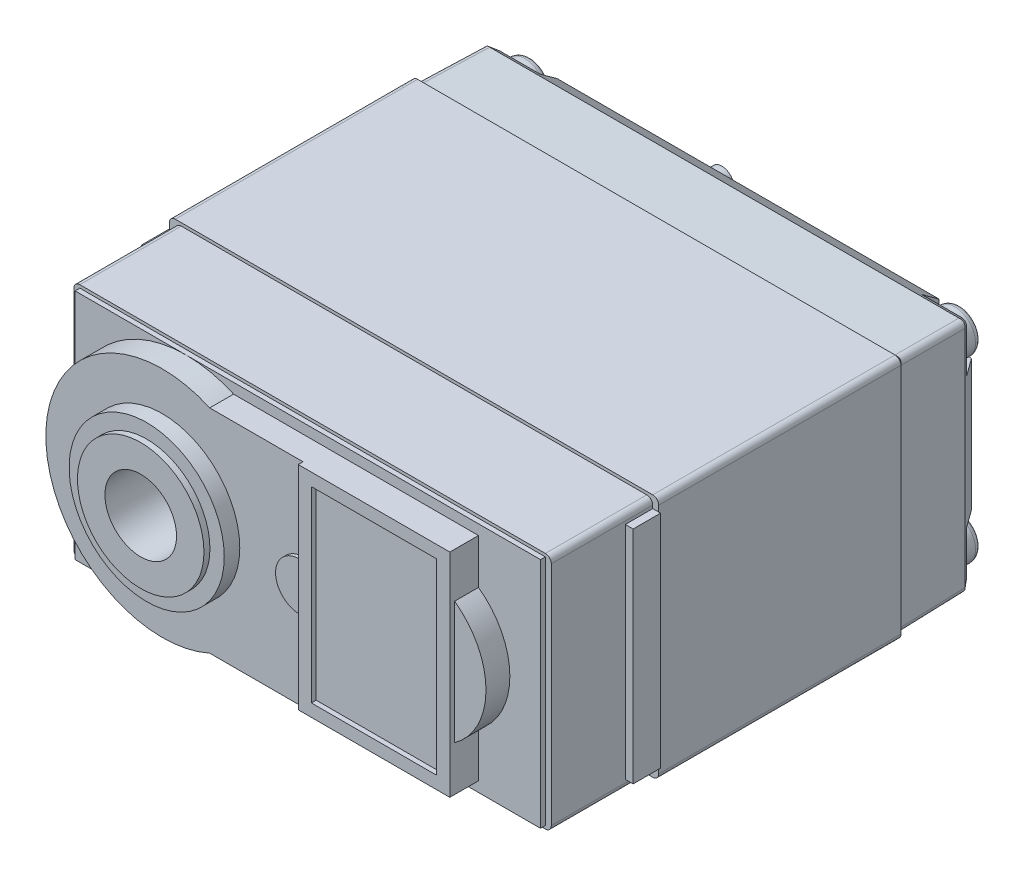
SolidWorks part; units mm, degrees
material "Du_servo"
ref_plane "Спереди" through (0, 0, 0) normal (0, 0, 1) x (1, 0, 0)
ref_plane "Сверху" through (0, 0, 0) normal (0, 1, 0) x (1, 0, 0)
ref_plane "Справа" through (0, 0, 0) normal (1, 0, 0) x (0, 0, -1)
sketch "Эскиз1" plane through (0, 0, 0) normal (0, 0, 1) x (1, 0, 0)
  line L1 (-20.5, 10.25) -> (20.5, 10.25)
  line L2 (-20.5, 10.25) -> (-20.5, -10.25)
  line L3 (-20.5, -10.25) -> (20.5, -10.25)
  line L4 (20.5, 10.25) -> (20.5, -10.25)
  line L5 (-20.5, 10.25) -> (20.5, -10.25) construction
  line L6 (-20.5, -10.25) -> (20.5, 10.25) construction
  point P0 (0, 0)
  dimension "D1" = 20.5
  dimension "D2" = 41
extrude "Бобышка-Вытянуть1" add sketch "Эскиз1" along normal blind 20.5
sketch "Эскиз2" plane through (0, 0, 20.5) normal (0, 0, 1) x (1, 0, 0)
  line L1 (-20, 10) -> (20, 10)
  line L2 (-20, 10) -> (-20, -10)
  line L3 (-20, -10) -> (20, -10)
  line L4 (20, 10) -> (20, -10)
  line L5 (-20, 10) -> (20, -10) construction
  line L6 (-20, -10) -> (20, 10) construction
  point P0 (0, 0)
  dimension "D1" = 20
  dimension "D2" = 40
extrude "Бобышка-Вытянуть2" add sketch "Эскиз2" along normal blind 8.5
sketch "Эскиз3" plane through (0, 0, 20.5) normal (0, 0, 1) x (1, 0, 0)
  line L0 (-20.5462, 9.25) -> (-20.5, -9.25)
  line L1 (-20.5462, 9.25) -> (20.6559, 9.25)
  line L3 (-20.5, -9.25) -> (20.6559, -9.25)
  line L5 (-20.5407, 7.0371) -> (20.6559, -7.0766) construction
  line L6 (-20.5056, -7.0251) -> (20.6559, 7.0766) construction
  line L7 (-20.5, 10.25) -> (-20.5, -10.25) construction
  line L8 (20.6559, 9.25) -> (20.6559, -9.25)
  point P0 (0, 0)
extrude "Бобышка-Вытянуть3" add sketch "Эскиз3" along normal blind 2.3
sketch "Эскиз4" plane through (0, 0, 0) normal (0, 0, -1) x (-1, 0, 0)
  line L1 (-20.25, 10) -> (20.25, 10)
  line L2 (-20.25, 10) -> (-20.25, -10)
  line L3 (-20.25, -10) -> (20.25, -10)
  line L4 (20.25, 10) -> (20.25, -10)
  line L5 (-20.25, 10) -> (20.25, -10) construction
  line L6 (-20.25, -10) -> (20.25, 10) construction
  point P0 (0, 0)
  dimension "D1" = 20
  dimension "D2" = 40.5
extrude "Бобышка-Вытянуть4" add sketch "Эскиз4" along normal blind 7.5 draft 1
sketch "Эскиз5" plane through (0, 0, 29) normal (0, 0, -1) x (-1, 0, 0)
  line L1 (-19.5, -9.75) -> (19.5, -9.75)
  line L2 (-19.5, -9.75) -> (-19.5, 9.75)
  line L3 (-19.5, 9.75) -> (19.5, 9.75)
  line L4 (19.5, -9.75) -> (19.5, 9.75)
  line L5 (-19.5, -9.75) -> (19.5, 9.75) construction
  line L6 (-19.5, 9.75) -> (19.5, -9.75) construction
  point P0 (0, 0)
  dimension "D1" = 19.5
  dimension "D2" = 39
extrude "Бобышка-Вытянуть5" add sketch "Эскиз5" against normal blind 0.4
sketch "Эскиз6" plane through (0, 0, 29.4) normal (0, 0, 1) x (1, 0, 0)
  line L1 (-28.6224, 0) -> (37.7217, 0) construction
  line L2 (-20.5462, 9.25) -> (-20.5, -9.25) construction
  line L3 (14.3, 8.9) -> (-6.2185, 8.9)
  line L4 (14.3, 8.9) -> (14.3, -8.9)
  line L5 (-19.5, -9.75) -> (-19.5, 9.75) construction
  line L6 (14.3, -8.9) -> (-6.2185, -8.9)
  circle A0 centre (-10.2, 0) radius 9.75 construction
  arc A1 (-6.2185, 8.9) -> (-6.2185, -8.9) centre (-10.2, 0) ccw
  point P13 (14.3, 0)
  dimension "D1" = 19.5
  dimension "D5" = 10.3231
  dimension "D3" = 8.9
  dimension "D4" = 33.8
extrude "Бобышка-Вытянуть6" add sketch "Эскиз6" along normal blind 2
sketch "Эскиз8" plane through (0, 0, 31.4) normal (0, 0, 1) x (1, 0, 0)
  line L1 (14.3, 8.9) -> (1.6, 8.9)
  line L2 (14.3, 8.9) -> (14.3, -8.9)
  line L3 (14.3, -8.9) -> (1.6, -8.9)
  line L4 (1.6, 8.9) -> (1.6, -8.9)
  line L5 (-6.2185, -8.9) -> (14.3, -8.9) construction
  line L6 (7.95, 8.9) -> (7.95, -8.9) construction
  line L8 (2.7, 7.85) -> (13.2, 7.85)
  line L9 (2.7, 7.85) -> (2.7, -7.85)
  line L10 (2.7, -7.85) -> (13.2, -7.85)
  line L11 (13.2, 7.85) -> (13.2, -7.85)
  line L12 (7.95, -7.85) -> (7.95, 7.85) construction
  line L13 (2.7, 0) -> (13.2, 0) construction
  point P10 (7.95, 0)
  dimension "D1" = 17.8
  dimension "D2" = 12.7
  dimension "D3" = 15.7
  dimension "D4" = 10.5
extrude "Бобышка-Вытянуть7" add sketch "Эскиз8" along normal blind 0.4
sketch "Эскиз9" plane through (0, 0, 31.4) normal (0, 0, 1) x (1, 0, 0)
  circle A0 centre (-10.2, 0) radius 6.5
  dimension "D1" = 13
extrude "Бобышка-Вытянуть8" add sketch "Эскиз9" along normal blind 1.3
sketch "Эскиз10" plane through (0, 0, 32.7) normal (0, 0, 1) x (1, 0, 0)
  circle A0 centre (-10.2, 0) radius 5.3
  dimension "D1" = 10.6
extrude "Бобышка-Вытянуть9" add sketch "Эскиз10" along normal blind 0.5
sketch "Эскиз11" plane through (0, 0, 33.2) normal (0, 0, 1) x (1, 0, 0)
  circle A0 centre (-10.2, 0) radius 3
  dimension "D1" = 6
extrude "Вырез-Вытянуть2" cut sketch "Эскиз11" against normal blind 5
sketch "Эскиз12" plane through (0, 0, 31.4) normal (0, 0, 1) x (1, 0, 0)
  line L0 (1.6, 8.9) -> (1.6, -8.9) construction
  line L1 (1.6, 2) -> (1.6, -2)
  circle A0 centre (1.6, 0) radius 2 construction
  arc A1 (1.6, 2) -> (1.6, -2) centre (1.6, 0) ccw
  dimension "D1" = 4
extrude "Бобышка-Вытянуть10" add sketch "Эскиз12" along normal blind 0.3
sketch "Эскиз13" plane through (0, 0, 29.4) normal (0, 0, 1) x (1, 0, 0)
  line L0 (14.3, -8.9) -> (14.3, 8.9) construction
  line L1 (14.3, -8.9) -> (14.3, 8.9) construction
  line L2 (14.3, 5.1324) -> (11.8319, 5.1324)
  line L3 (11.8319, 5.1324) -> (11.8319, -5.1324)
  line L4 (11.8319, -5.1324) -> (14.3, -5.1324)
  circle A0 centre (10.6069, 0) radius 6.323 construction
  arc A1 (14.3, 5.1324) -> (14.3, -5.1324) centre (10.6069, 0) cw
  dimension "D1" = 12.6459
extrude "Бобышка-Вытянуть11" add sketch "Эскиз13" along normal blind 2
fillet "Скругление3" radius 0.5 8 edges at (-20, -10, 24.75) (-20.5, -10.25, 10.25) (-20, 10, 24.75) (-20.5, 10.25, 10.25) (20.5, 10.25, 10.25) (20, 10, 24.75) (20.5, -10.25, 10.25) (20, -10, 24.75)
chamfer "Фаска3" distance 0.2 angle 45 8 edges at (0, 10.25, 0) (-20.3536, 10.1036, 0) (20.3536, 10.1036, 0) (-20.5, 0, 0) (20.5, 0, 0) (-20.3536, -10.1036, 0) (20.3536, -10.1036, 0) (0, -10.25, 0)
chamfer "Фаска4" distance 2 angle 35 4 edges at (0, -9.8691, -7.5) (20.1191, 0, -7.5) (0, 9.8691, -7.5) (-20.1191, 0, -7.5)
sketch "Эскиз15" plane through (0, 0, -7.5) normal (0, 0, -1) x (-1, 0, 0)
  line L0 (20, -7.5) -> (16, -7.5) construction
  line L1 (-18, 7.5) -> (18, 7.5) construction
  line L2 (-18, 7.5) -> (-18, -7.5) construction
  line L3 (-18, -7.5) -> (18, -7.5) construction
  line L4 (18, 7.5) -> (18, -7.5) construction
  line L5 (0, -7.5) -> (0, 7.5) construction
  line L6 (-18, 0) -> (18, 0) construction
  line L7 (-20, 9.5) -> (-16, 9.5)
  line L8 (-20, 9.5) -> (-20, 5.5)
  line L9 (-20, 5.5) -> (-16, 5.5)
  line L10 (-16, 9.5) -> (-16, 5.5)
  line L11 (-18, 5.5) -> (-18, 9.5) construction
  line L12 (-20, 7.5) -> (-16, 7.5) construction
  line L13 (20, 9.5) -> (16, 9.5)
  line L14 (20, 9.5) -> (20, 5.5)
  line L15 (20, 5.5) -> (16, 5.5)
  line L16 (16, 9.5) -> (16, 5.5)
  line L17 (18, 5.5) -> (18, 9.5) construction
  line L18 (20, 7.5) -> (16, 7.5) construction
  line L19 (18, -5.5) -> (18, -9.5) construction
  line L20 (16, -9.5) -> (16, -5.5)
  line L21 (20, -5.5) -> (16, -5.5)
  line L22 (20, -9.5) -> (20, -5.5)
  line L23 (20, -9.5) -> (16, -9.5)
  line L24 (-20, -7.5) -> (-16, -7.5) construction
  line L25 (-18, -5.5) -> (-18, -9.5) construction
  line L26 (-16, -9.5) -> (-16, -5.5)
  line L27 (-20, -5.5) -> (-16, -5.5)
  line L28 (-20, -9.5) -> (-20, -5.5)
  line L29 (-20, -9.5) -> (-16, -9.5)
  point P0 (0, 0)
  dimension "D1" = 15
  dimension "D2" = 36
  dimension "D3" = 4
  dimension "D4" = 4
extrude "Вырез-Вытянуть3" cut sketch "Эскиз15" against normal blind 1.5
fillet "Скругление4" radius 2 4 edges at (16, -5.5, -6.75) (-16, -5.5, -6.75) (-16, 5.5, -6.75) (16, 5.5, -6.75)
fillet "Скругление5" radius 0.5 8 edges at (-19.952, 9.702, -5.7783) (-20.2025, 9.9525, -2.7227) (-20.2025, -9.9525, -2.7227) (-19.952, -9.702, -5.7783) (20.2025, 9.9525, -2.7227) (19.952, 9.702, -5.7783) (20.2025, -9.9525, -2.7227) (19.952, -9.702, -5.7783)
sketch "Эскиз16" plane through (0, 0, -6) normal (0, 0, -1) x (-1, 0, 0)
  line L1 (-18, 7.5) -> (18, 7.5) construction
  line L2 (-18, 7.5) -> (-18, -7.5) construction
  line L3 (-18, -7.5) -> (18, -7.5) construction
  line L4 (18, 7.5) -> (18, -7.5) construction
  line L5 (0, -7.5) -> (0, 7.5) construction
  line L6 (-18, 0) -> (18, 0) construction
  circle A0 centre (-18, 7.5) radius 1.75
  circle A1 centre (18, 7.5) radius 1.75
  circle A2 centre (18, -7.5) radius 1.75
  circle A3 centre (-18, -7.5) radius 1.75
  point P0 (0, 0)
  dimension "D3" = 3.5
  dimension "D4" = 3.5
  dimension "D5" = 3.5
  dimension "D6" = 3.5
  dimension "D1" = 15
  dimension "D2" = 36
extrude "Бобышка-Вытянуть13" add sketch "Эскиз16" along normal blind 1.3 separate body
fillet "Скругление6" radius 0.5 1 edges at (16.25, 7.5, -7.3)
fillet "Скругление7" radius 0.5 1 edges at (-19.75, 7.5, -7.3)
fillet "Скругление8" radius 0.5 1 edges at (-19.75, -7.5, -7.3)
fillet "Скругление9" radius 0.5 1 edges at (16.25, -7.5, -7.3)
sketch "Эскиз17" plane through (0, 0, -7.5) normal (0, 0, -1) x (-1, 0, 0)
  line L0 (0, 16.9028) -> (0, -15.463) construction
  line L1 (0, -15.463) -> (27, 0) construction
  line L3 (27, 0) -> (-27, 0) construction
  line L5 (-18.9, -7.5) -> (-17.1, -7.5) construction
  line L6 (-18.25, 8.4) -> (-17.75, 8.4)
  line L7 (-18.25, 8.4) -> (-18.25, 6.6)
  line L8 (-18.25, 6.6) -> (-17.75, 6.6)
  line L9 (-17.75, 8.4) -> (-17.75, 6.6)
  line L10 (-18, 6.6) -> (-18, 8.4) construction
  line L11 (-18.25, 7.5) -> (-17.75, 7.5) construction
  line L12 (-18.9, 7.75) -> (-17.1, 7.75)
  line L13 (-18.9, 7.75) -> (-18.9, 7.25)
  line L14 (-18.9, 7.25) -> (-17.1, 7.25)
  line L15 (-17.1, 7.75) -> (-17.1, 7.25)
  line L16 (-18, 7.25) -> (-18, 7.75) construction
  line L17 (-18.9, 7.5) -> (-17.1, 7.5) construction
  line L18 (-18, -7.25) -> (-18, -7.75) construction
  line L19 (-18.25, -7.5) -> (-17.75, -7.5) construction
  line L20 (-18, -6.6) -> (-18, -8.4) construction
  line L21 (-17.1, -7.75) -> (-17.1, -7.25)
  line L22 (-18.9, -7.25) -> (-17.1, -7.25)
  line L23 (-18.9, -7.75) -> (-18.9, -7.25)
  line L24 (-18.9, -7.75) -> (-17.1, -7.75)
  line L25 (-17.75, -8.4) -> (-17.75, -6.6)
  line L26 (-18.25, -6.6) -> (-17.75, -6.6)
  line L27 (-18.25, -8.4) -> (-18.25, -6.6)
  line L28 (-18.25, -8.4) -> (-17.75, -8.4)
  line L29 (18, -6.6) -> (18, -8.4) construction
  line L30 (18.25, -7.5) -> (17.75, -7.5) construction
  line L31 (18, -7.25) -> (18, -7.75) construction
  line L32 (18.9, 7.5) -> (17.1, 7.5) construction
  line L33 (18, 7.25) -> (18, 7.75) construction
  line L34 (18.25, 7.5) -> (17.75, 7.5) construction
  line L35 (18, 6.6) -> (18, 8.4) construction
  line L36 (18.9, -7.5) -> (17.1, -7.5) construction
  line L37 (18.25, -8.4) -> (17.75, -8.4)
  line L38 (18.25, -8.4) -> (18.25, -6.6)
  line L39 (18.25, -6.6) -> (17.75, -6.6)
  line L40 (17.75, -8.4) -> (17.75, -6.6)
  line L41 (18.9, -7.75) -> (17.1, -7.75)
  line L42 (18.9, -7.75) -> (18.9, -7.25)
  line L43 (18.9, -7.25) -> (17.1, -7.25)
  line L44 (17.1, -7.75) -> (17.1, -7.25)
  line L45 (17.1, 7.75) -> (17.1, 7.25)
  line L46 (18.9, 7.25) -> (17.1, 7.25)
  line L47 (18.9, 7.75) -> (18.9, 7.25)
  line L48 (18.9, 7.75) -> (17.1, 7.75)
  line L49 (17.75, 8.4) -> (17.75, 6.6)
  line L50 (18.25, 6.6) -> (17.75, 6.6)
  line L51 (18.25, 8.4) -> (18.25, 6.6)
  line L52 (18.25, 8.4) -> (17.75, 8.4)
  point P9 (-18, 7.5)
  point P13 (-18, 7.5)
  point P39 (-18, -7.5)
  point P77 (18, -7.5)
  point P78 (18, 7.5)
  dimension "D1" = 1.8
  dimension "D2" = 0.5
  dimension "D3" = 0.5
  dimension "D4" = 1.8
extrude "Вырез-Вытянуть4" cut sketch "Эскиз17" against normal blind 1.3 draft 3 contours L7 L8 L9 L6 | L12 L15 L14 L13 | L51 L50 L49 L52 | L48 L45 L46 L47 | L43 L44 L41 L42 | L38 L39 L40 L37 | L25 L26 L27 L28 | L22 L21 L24 L23
sketch "Эскиз18" plane through (-20.5, 0, 0) normal (-1, 0, 0) x (0, 0, 1)
  line L1 (-3.7868, 3.5) -> (0.2132, 3.5)
  line L2 (-3.7868, 3.5) -> (-3.7868, -3.5)
  line L3 (-3.7868, -3.5) -> (0.2132, -3.5)
  line L4 (0.2132, 3.5) -> (0.2132, -3.5)
  line L5 (-1.7868, -3.5) -> (-1.7868, 3.5) construction
  line L6 (-3.7868, 0) -> (0.2132, 0) construction
  point P0 (-1.7868, 0)
  dimension "D1" = 7
  dimension "D2" = 4
extrude "Бобышка-Вытянуть14" add sketch "Эскиз18" along normal blind 4 draft 4 and the other way blind 2
fillet "Скругление10" radius 0.3 4 edges at (-22.5, -3.3601, -3.647) (-22.5, -3.3601, 0.0733) (-22.5, 3.3601, 0.0733) (-22.5, 3.3601, -3.647)
sketch "Эскиз19" plane through (-24.5, 0, 0) normal (-1, 0, 0) x (0, 0, 1)
  line L0 (-1.7868, 3.2203) -> (-1.7868, -3.2203) construction
  line L1 (-0.3658, 3.2203) -> (-3.2078, 3.2203) construction
  line L2 (-3.2078, -3.2203) -> (-0.3658, -3.2203) construction
  circle A0 centre (-1.7868, 0) radius 0.75
  circle A1 centre (-1.7868, 1.55) radius 0.75
  circle A2 centre (-1.7868, -1.55) radius 0.75
  dimension "D1" = 1.5
  dimension "D2" = 1.5
  dimension "D3" = 1.5
  dimension "D4" = 1.55
  dimension "D5" = 1.55
extrude "Бобышка-Вытянуть15" add sketch "Эскиз19" along normal blind 3
sketch "Sketch1" plane through (0, 0, -7.5) normal (0, 0, -1) x (-1, 0, 0)
  line L0 (20.5, 9.75) -> (20.5, 3.2887) construction
  circle A0 centre (10.2, 0) radius 1
  dimension "D1" = 2
  dimension "D2" = 10.3
extrude "Boss-Extrude1" add sketch "Sketch1" along normal blind 8
